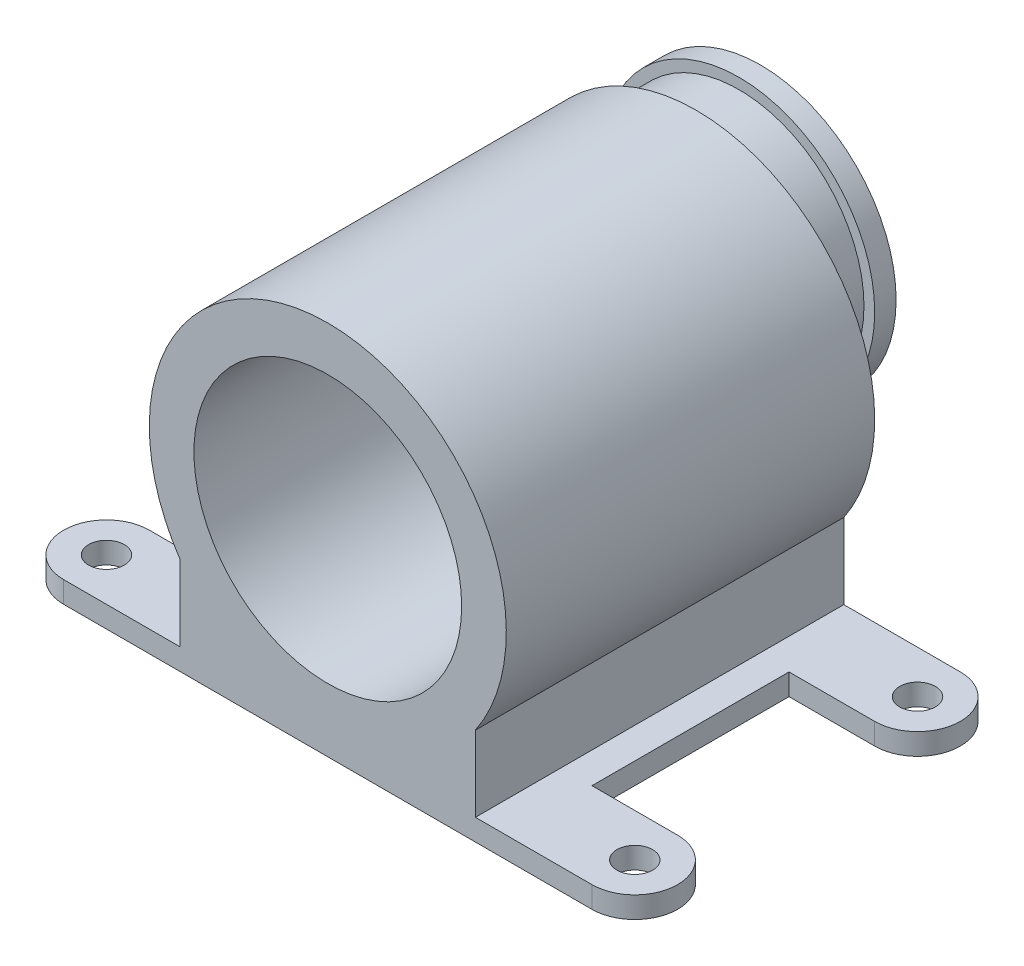
SolidWorks part; units mm, degrees
ref_plane "Alzado" through (0, 0, 0) normal (0, 0, 1) x (1, 0, 0)
ref_plane "Planta" through (0, 0, 0) normal (0, 1, 0) x (1, 0, 0)
ref_plane "Vista lateral" through (0, 0, 0) normal (1, 0, 0) x (0, 0, -1)
sketch "Croquis1" plane through (0, 0, 0) normal (0, 0, 1) x (1, 0, 0)
  circle A1 centre (0, 0) radius 21.1
  dimension "D2" = 42.2
extrude "Saliente-Extruir1" add sketch "Croquis1" along normal blind 51.6
sketch "Croquis2" plane through (0, 0, 51.6) normal (0, 0, 1) x (1, 0, 0)
  circle A0 centre (0, 0) radius 18.75
  dimension "D1" = 37.5
extrude "Cortar-Extruir1" cut sketch "Croquis2" against normal blind 48.6
sketch "Croquis3" plane through (0, 0, 0) normal (0, 0, -1) x (-1, 0, 0)
  circle A1 centre (0, 0) radius 21.1 construction
  circle A2 centre (0, 0) radius 21.1
sketch "Croquis5" plane through (0, 0, 3) normal (0, 0, 1) x (1, 0, 0)
  line L0 (0, -18.75) -> (0, 7) construction
  line L1 (0, 7) -> (0, 18.75) construction
  circle A0 centre (0, 0) radius 18.75
  circle A1 centre (0, 7) radius 6.275
  circle A3 centre (0, 7) radius 7.775
  dimension "D1" = 25.75
  dimension "D2" = 12.55
  dimension "D3" = 15.55
extrude "Saliente-Extruir3" add sketch "Croquis5" against normal blind 6 contours A3 A1 region at (-7.5551, 7, 3)
sketch "Croquis6" plane through (0, 0, 0) normal (0, 0, -1) x (-1, 0, 0)
  circle A0 centre (0, 7) radius 6.275
extrude "Cortar-Extruir2" cut sketch "Croquis6" against normal blind 66
sketch "Croquis8" plane through (0, 0, 0) normal (0, 0, -1) x (-1, 0, 0)
  circle A1 centre (0, 0) radius 21.1 construction
  circle A2 centre (0, 0) radius 21.1
sketch "Croquis9" plane through (0, 0, 0) normal (0, 0, -1) x (-1, 0, 0)
sketch "Croquis10" plane through (0, 0, 0) normal (0, 0, -1) x (-1, 0, 0)
  circle A0 centre (0, 0) radius 21.1
  circle A1 centre (0, 0) radius 25
  dimension "D1" = 50
extrude "Saliente-Extruir4" add sketch "Croquis10" against normal up to surface (51.6 mm away) up to face at (18.75, 0, 51.6)
sketch "Croquis11" plane through (0, 0, 0) normal (0, 0, -1) x (-1, 0, 0)
  circle A0 centre (0, 7) radius 16
  circle A1 centre (0, 7) radius 17.5
  dimension "D1" = 32
  dimension "D3" = 35
extrude "Saliente-Extruir5" add sketch "Croquis11" along normal blind 9
sketch "Croquis12" plane through (0, 0, -9) normal (0, 0, -1) x (-1, 0, 0)
  circle A0 centre (0, 7) radius 19
  circle A3 centre (0, 7) radius 17.5 construction
  circle A4 centre (0, 7) radius 17.5
  dimension "D1" = 38
extrude "Saliente-Extruir6" add sketch "Croquis12" against normal blind 3
sketch "Croquis13" plane through (0, 0, 0) normal (0, 0, -1) x (-1, 0, 0)
  line L0 (0, -25) -> (-25, -25)
  line L1 (-25, -25) -> (-25, -27.6328)
  line L2 (-25, -27.6328) -> (25, -27.6328)
  line L3 (25, -27.6328) -> (25, -25)
  line L4 (25, -25) -> (0, -25)
  line L5 (-20.6738, -14.0568) -> (20.6738, -14.0568)
  line L6 (-20.6738, -14.0568) -> (-20.6738, -25)
  line L7 (20.6738, -14.0568) -> (20.6738, -25)
  circle A1 centre (0, 0) radius 25 construction
  circle A2 centre (0, 0) radius 25
  circle M3 centre (0, 0) radius 25
extrude "Saliente-Extruir7" add sketch "Croquis13" against normal up to surface (51.6 mm away) contours L6 L0 M3 | L7 L4 M3 | L3 L4 L0 L1 L2 region at (0, -26.3164, 0) region at (-15.7585, -21.8919, 0) region at (15.7585, -21.8919, 0) up to face at (18.75, 0, 51.6)
sketch "Croquis14" plane through (25, 0, 0) normal (1, 0, 0) x (0, 0, -1)
  line L0 (-51.6, -27.6328) -> (-51.6, -24.6328)
  line L5 (-51.6, -14.0568) -> (-51.6, -25) construction
  line L6 (-51.6, -24.6328) -> (0, -24.6328)
  line L7 (0, -14.0568) -> (0, -25) construction
  line L8 (0, -24.6328) -> (0, -27.6328)
  line L9 (0, -27.6328) -> (-51.6, -27.6328)
  dimension "D1" = 3
extrude "Saliente-Extruir8" add sketch "Croquis14" against normal up to surface (50 mm away) up to face at (-25, -26.3164, 25.8)
sketch "Croquis16" plane through (25, 0, 0) normal (1, 0, 0) x (0, 0, -1)
  line L0 (-51.6, -27.6328) -> (0, -27.6328) construction
  line L1 (-51.6, -24.6328) -> (-39.6, -24.6328)
  line L2 (-51.6, -24.6328) -> (-51.6, -27.6328)
  line L3 (-51.6, -27.6328) -> (-39.6, -27.6328)
  line L4 (-39.6, -24.6328) -> (-39.6, -27.6328)
  line L5 (0, -24.6328) -> (-51.6, -24.6328) construction
  line L6 (0, -27.6328) -> (-12, -27.6328)
  line L7 (0, -27.6328) -> (0, -24.6328)
  line L8 (0, -24.6328) -> (-12, -24.6328)
  line L9 (-12, -27.6328) -> (-12, -24.6328)
  dimension "D1" = 12
  dimension "D2" = 12
extrude "Saliente-Extruir9" add sketch "Croquis16" along normal blind 12
sketch "Croquis18" plane through (0, -24.6328, 0) normal (0, 1, 0) x (1, 0, 0)
  line L0 (37, -39.6) -> (37, -51.6) construction
  line L1 (37, -39.6) -> (25, -39.6) construction
  line L2 (37, -39.6) -> (37, -51.6)
  line L3 (37, 0) -> (37, -12) construction
  circle A0 centre (37, -45.6) radius 6
  circle A1 centre (37, -6) radius 6
  line M4 (37, -51.6) -> (37, -39.6)
  line M8 (37, -12) -> (37, 0)
  dimension "D1" = 12
extrude "Saliente-Extruir11" add sketch "Croquis18" against normal up to surface (3 mm away) contours A1 M8 | A0 M4 region at (39.5465, -24.6328, 45.6) region at (39.5465, -24.6328, 6) up to face at (18.5, -27.6328, 25.8)
sketch "Croquis19" plane through (0, -24.6328, 0) normal (0, 1, 0) x (1, 0, 0)
  line L0 (43, -45.6) -> (37, -45.6) construction
  line L1 (43, -6) -> (37, -6) construction
  arc A0 (37, -51.6) -> (37, -39.6) centre (37, -45.6) ccw construction
  arc A1 (37, -12) -> (37, 0) centre (37, -6) ccw construction
  circle A2 centre (37, -6) radius 2.5
  circle A3 centre (37, -45.6) radius 2.5
  dimension "D1" = 5
  dimension "D2" = 5
extrude "Cortar-Extruir5" cut sketch "Croquis19" against normal blind 15
sketch "Croquis20" plane through (-25, 0, 0) normal (-1, 0, 0) x (0, 0, 1)
  line L0 (51.6, -27.6328) -> (0, -27.6328) construction
  line L1 (0, -24.6328) -> (12, -24.6328)
  line L2 (0, -24.6328) -> (0, -27.6328)
  line L3 (0, -27.6328) -> (12, -27.6328)
  line L4 (12, -24.6328) -> (12, -27.6328)
  line L5 (0, -24.6328) -> (51.6, -24.6328) construction
  line L6 (51.6, -27.6328) -> (39.6, -27.6328)
  line L7 (51.6, -27.6328) -> (51.6, -24.6328)
  line L8 (51.6, -24.6328) -> (39.6, -24.6328)
  line L9 (39.6, -27.6328) -> (39.6, -24.6328)
  dimension "D1" = 12
  dimension "D2" = 12
extrude "Saliente-Extruir12" add sketch "Croquis20" along normal blind 12
sketch "Croquis21" plane through (0, -24.6328, 0) normal (0, 1, 0) x (1, 0, 0)
  line L0 (-37, -12) -> (-37, 0) construction
  line L1 (-37, -51.6) -> (-37, -39.6) construction
  line L2 (-37, 0) -> (-37, -12)
  line L3 (-37, -39.6) -> (-37, -51.6)
  circle A0 centre (-37, -6) radius 6
  circle A1 centre (-37, -45.6) radius 6
  line M3 (-37, 0) -> (-37, -12)
  line M7 (-37, -39.6) -> (-37, -51.6)
  dimension "D1" = 12
  dimension "D2" = 12
extrude "Saliente-Extruir13" add sketch "Croquis21" against normal up to surface (3 mm away) contours A0 M3 | A1 M7 region at (-39.5465, -24.6328, 6) region at (-39.5465, -24.6328, 45.6) up to face at (37, -27.6328, 3.5)
sketch "Croquis22" plane through (0, -24.6328, 0) normal (0, 1, 0) x (1, 0, 0)
  line L0 (-43, -6) -> (-37, -6) construction
  line L1 (-43, -45.6) -> (-37, -45.6) construction
  arc A0 (-37, 0) -> (-37, -12) centre (-37, -6) ccw construction
  arc A1 (-37, -39.6) -> (-37, -51.6) centre (-37, -45.6) ccw construction
  circle A2 centre (-37, -6) radius 2.5
  circle A3 centre (-37, -45.6) radius 2.5
  dimension "D1" = 5
  dimension "D2" = 5
extrude "Cortar-Extruir6" cut sketch "Croquis22" against normal blind 12
